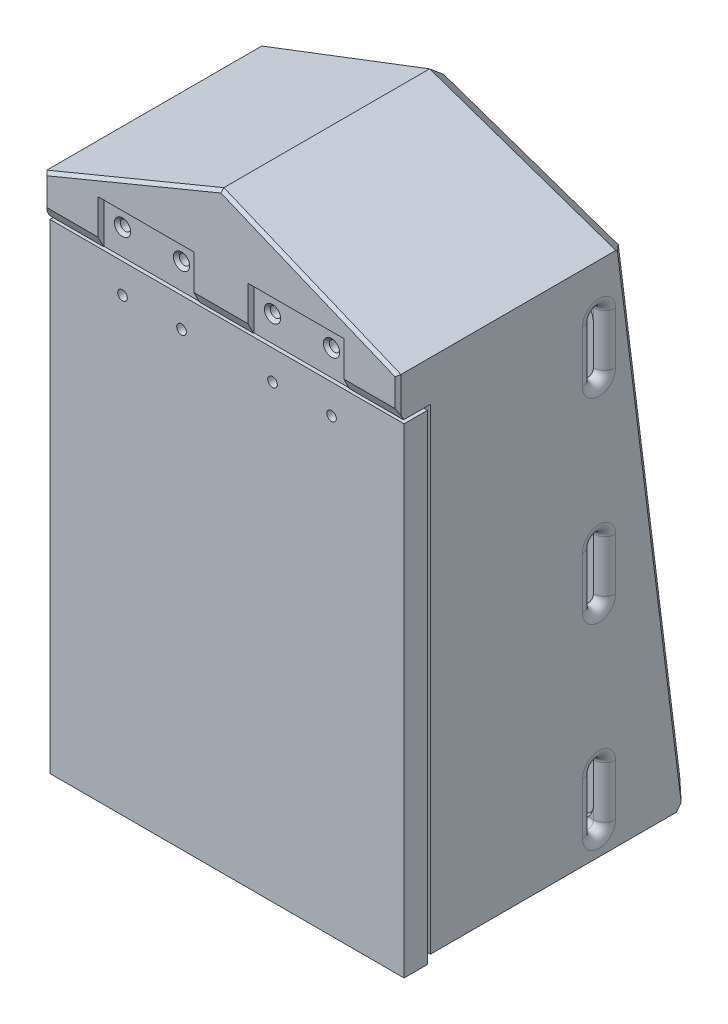
SolidWorks part; units mm, degrees
other "House"
other "Door"
other "Cover" parameters "D1"=134.3446, "D2"=7.568, "D3"=4.0473, "D4"=11.5
ref_plane "Front Plane" through (0, 0, 0) normal (0, 0, 1) x (1, 0, 0)
ref_plane "Top Plane" through (0, 0, 0) normal (0, 1, 0) x (1, 0, 0)
ref_plane "Right Plane" through (0, 0, 0) normal (1, 0, 0) x (0, 0, -1)
sketch "Sketch1" plane through (0, 0, 0) normal (0, 0, 1) x (1, 0, 0)
  line L0 (-48, 73.5589) -> (-48, -66.5589)
  line L1 (-45, -61.5589) -> (45, -61.5589)
  line L2 (-45, -61.5589) -> (-45, 61.5589)
  line L3 (-45, 61.5589) -> (45, 61.5589)
  line L4 (45, -61.5589) -> (45, 61.5589)
  line L5 (0, 61.5589) -> (0, -61.5589) construction
  line L6 (-45, 0) -> (45, 0) construction
  line L7 (-48, -66.5589) -> (48, -66.5589)
  line L8 (48, -66.5589) -> (48, 73.5589)
  line L9 (48, 73.5589) -> (0, 93.4411)
  line L10 (0, 93.4411) -> (-48, 73.5589)
  point P0 (0, 0)
  dimension "D1" = 160
  dimension "D2" = 90
  dimension "D3" = 22.5
  dimension "D4" = 12
  dimension "D5" = 5
  dimension "D6" = 3
  dimension "D7" = 123.1177
extrude "main-extrude" add sketch "Sketch1" along normal blind 60
sketch "Sketch2" plane through (0, 0, 0) normal (0, 0, 1) x (1, 0, 0)
  line L0 (48, -66.5589) -> (48, 73.5589) construction
  line L1 (-48, -66.5589) -> (48, -66.5589) construction
  line L2 (-48, 73.5589) -> (-48, -66.5589) construction
  line L3 (48, 73.5589) -> (0, 93.4411) construction
  line L4 (0, 93.4411) -> (-48, 73.5589) construction
  line L5 (48, -66.5589) -> (48, 73.5589)
  line L6 (-48, -66.5589) -> (48, -66.5589)
  line L7 (-48, 73.5589) -> (-48, -66.5589)
  line L8 (48, 73.5589) -> (0, 93.4411)
  line L9 (0, 93.4411) -> (-48, 73.5589)
extrude "rear-extrude" add sketch "Sketch2" against normal blind 20
sketch "Sketch24" plane through (0, 0, 0) normal (1, 0, 0) x (0, 0, -1)
  line L0 (0, 93.4411) -> (20, -66.5589)
  line L1 (-60, 93.4411) -> (20, 93.4411) construction
  line L2 (20, -66.5589) -> (20, 93.4411)
  line L3 (20, 93.4411) -> (0, 93.4411)
  point P4 (0, 0)
  point P7 (0, 0)
extrude "rear-angle-cut" cut sketch "Sketch24" against normal through all both and the other way through all
sketch "Sketch6" [suppressed] plane through (0, -66.5589, 0) normal (0, -1, 0) x (1, 0, 0)
  line L0 (48, 22.9375) -> (52, 22.9375)
  line L1 (62.9375, 15) -> (62.9375, 22.9375)
  line L2 (52, 22.9375) -> (55, 22.9375)
  line L3 (-48, -5) -> (48, -5) construction
  line L4 (62.9375, 15) -> (62.9375, -5)
  line L5 (62.9375, -5) -> (48, -5)
  line L6 (48, 60) -> (48, -5) construction
  line L7 (48, -5) -> (48, 22.9375)
  line L8 (62.9375, 22.9375) -> (55, 22.9375)
  circle A0 centre (62.9375, 22.9375) radius 7.9375 construction
  arc A1 (62.9375, 15) -> (55, 22.9375) centre (62.9375, 22.9375) cw construction
  point P3 (62.9375, 15)
  dimension "D3" = 15.875
  dimension "D1" = 4
  dimension "D2" = 3
  dimension "D4" = 20
extrude "Boss-Extrude3" [suppressed] add sketch "Sketch6" against normal up to surface (140.1177 mm away)
sketch "Sketch19" [suppressed] plane through (62.9375, 0, 0) normal (1, 0, 0) x (0, 0, -1)
  line L0 (-7.4977, -71.6348) -> (-21.3388, 52.9783) construction
  line L2 (-22.9375, 67.3716) -> (-32.8764, 66.2676) construction
  line L3 (-7.9389, -67.6628) -> (2, -66.5589) construction
  line L6 (5, -66.5589) -> (-22.9375, -66.5589) construction
  dimension "D1" = 10
  dimension "D3" = 3
ref_plane "Plane6" [suppressed] through (62.9375, -67.6628, 7.9389) normal (0, 0.9939, 0.1104) x (1, 0, 0)
sketch "Sketch20" [suppressed] plane through (62.9375, -67.6628, 7.9389) normal (0, 0.9939, 0.1104) x (1, 0, 0)
  line L0 (10, 0) -> (10, -24.5702)
  line L3 (10, -24.5702) -> (-14.9375, -24.5702)
  line L4 (21.2132, 0) -> (-21.2132, 42.4264)
  line L5 (-21.2132, 42.4264) -> (21.2132, 42.4264)
  line L6 (21.2132, 42.4264) -> (21.2132, 0)
  line L7 (0, 0) -> (10.6066, 10.6066) construction
  line L8 (-10, 0) -> (-10, -5)
  line L9 (-10, -5) -> (-14.9375, -5)
  line L10 (-14.9375, -5) -> (-14.9375, -24.5702)
  circle A0 centre (0, 0) radius 10 construction
  circle A3 centre (0, 0) radius 15 construction
  arc A4 (-10, 0) -> (10, 0) centre (0, 0) cw
  point P16 (10.6066, 10.6066)
  point P18 (10.6066, 10.6066)
  point P19 (10.6066, 10.6066)
  point P20 (10.6066, 10.6066)
  point P21 (10.6066, 10.6066)
  point P22 (7.0711, 7.0711)
  dimension "D1" = 20
  dimension "D2" = 5
  dimension "D3" = 5
extrude "Cut-Extrude9" [suppressed] cut sketch "Sketch20" along normal through all
ref_plane "Plane1" [suppressed] through (62.9375, -47.7851, 10.1468) normal (0, 0.9939, 0.1104) x (1, 0, 0)
ref_plane "Plane2" [suppressed] through (0, 0, 0) normal (0, 0.9939, 0.1104) x (1, 0, 0)
sketch "Sketch7" [suppressed] plane through (62.9375, -47.7851, 10.1468) normal (0, 0.9939, 0.1104) x (1, 0, 0)
  line L0 (-14.9375, -15) -> (-11.9375, -15)
  line L2 (-14.9375, -5) -> (-10, -5) construction
  line L4 (-11.9375, -15) -> (-11.9375, -5)
  line L5 (-11.9375, -5) -> (-11.9375, 0)
  line L6 (-14.9375, -15) -> (-14.9375, 0)
  line L7 (0, 11.9375) -> (10, 11.9375)
  line L8 (10, 11.9375) -> (10, 14.9375)
  line L9 (10, 14.9375) -> (0, 14.9375)
  line L10 (-14.9375, -51.6211) -> (-14.9375, -5) construction
  arc A2 (-11.9375, 0) -> (0, 11.9375) centre (0, 0) cw
  arc A3 (0, 14.9375) -> (-14.9375, 0) centre (0, 0) ccw
  circle A4 centre (0, 0) radius 10 construction
  dimension "D1" = 3
  dimension "D2" = 10
  dimension "D3" = 10
extrude "Cut-Extrude10" [suppressed] cut sketch "Sketch7" along normal blind 14
pattern_linear "LPattern1" [suppressed] count 2 spacing 95 along (0, 0.9939, 0.1104)
fillet "Fillet2" [suppressed] radius 3
sketch "Sketch9" plane through (0, -66.5589, 0) normal (0, -1, 0) x (1, 0, 0)
  line L0 (-48, 0) -> (48, 0) construction
  line L3 (-30, 3) -> (0, 3) construction
  line L4 (0, 3) -> (30, 3) construction
  circle A0 centre (-30, 3) radius 3
  circle A1 centre (0, 3) radius 3
  circle A2 centre (30, 3) radius 3
  dimension "D1" = 6
  dimension "D2" = 30
extrude "inner-drain-holes" cut sketch "Sketch9" against normal blind 15
sketch "Sketch4" plane through (0, 0, 60) normal (0, 0, 1) x (1, 0, 0)
  line L0 (-48, 73.5589) -> (-48, -66.5589) construction
  line L1 (-48, 61.5589) -> (48, 61.5589) construction
  line L2 (-48, 61.5589) -> (-48, -66.5589)
  line L3 (-48, -66.5589) -> (48, -66.5589)
  line L4 (48, 61.5589) -> (48, -66.5589)
  line L5 (48, -66.5589) -> (48, 73.5589) construction
  line L6 (-48, 61.5589) -> (-48, 62.5589)
  line L7 (-48, 73.5589) -> (-48, -66.5589) construction
  line L8 (-48, 62.5589) -> (48, 62.5589)
  line L9 (48, -66.5589) -> (48, 73.5589) construction
  line L10 (48, 62.5589) -> (48, 61.5589)
  dimension "D1" = 1
extrude "Cut-Extrude2" cut sketch "Sketch4" against normal blind 8
sketch "Sketch5" plane through (0, 0, 60) normal (0, 0, 1) x (1, 0, 0)
  line L0 (-33.3333, 61.5589) -> (-7.3333, 61.5589) construction
  line L1 (-33.3333, 48.0589) -> (-7.3333, 48.0589)
  line L2 (-33.3333, 48.0589) -> (-33.3333, 75.0589)
  line L3 (-33.3333, 75.0589) -> (-7.3333, 75.0589)
  line L4 (-7.3333, 48.0589) -> (-7.3333, 75.0589)
  line L5 (-20.3333, 75.0589) -> (-20.3333, 48.0589) construction
  line L6 (-33.3333, 61.5589) -> (-7.3333, 61.5589) construction
  line L7 (-45, 61.5589) -> (45, 61.5589) construction
  line L8 (-48, 61.5589) -> (48, 61.5589) construction
  line L9 (0, -987.8214) -> (0, 49012.1786) construction
  line L10 (-33.3333, 61.5589) -> (-48, 61.5589) construction
  line L11 (-48, 73.5589) -> (-48, -66.5589) construction
  line L12 (33.3333, 75.0589) -> (7.3333, 75.0589)
  line L13 (7.3333, 48.0589) -> (7.3333, 75.0589)
  line L14 (33.3333, 48.0589) -> (7.3333, 48.0589)
  line L15 (33.3333, 48.0589) -> (33.3333, 75.0589)
  line L16 (-7.3333, 61.5589) -> (7.3333, 61.5589) construction
  point P0 (-20.3333, 61.5589)
  dimension "D1" = 27
  dimension "D2" = 26
extrude "Cut-Extrude3" cut sketch "Sketch5" against normal offset from surface (1.65 mm away) 6.35 up to face at (0, 0, 52)
sketch "Sketch15" plane through (0, 0, 58.35) normal (0, 0, 1) x (1, 0, 0)
  line L0 (-28.3333, 69.5589) -> (-12.3333, 69.5589) construction
  line L1 (0, -934.1648) -> (0, 49065.8352) construction
  line L2 (0, -200987.8214) -> (0, 249012.1786) construction
  line L3 (-20.3333, 75.0589) -> (-20.3333, 48.0589) construction
  line L4 (-33.3333, 61.5589) -> (-7.3333, 61.5589) construction
  circle A0 centre (-28.3333, 69.5589) radius 1.4
  circle A1 centre (-12.3333, 69.5589) radius 1.4
  circle A2 centre (28.3333, 69.5589) radius 1.4
  circle A3 centre (12.3333, 69.5589) radius 1.4
  point P8 (-20.3333, 69.5589)
  dimension "D1" = 2.8
  dimension "D2" = 16
  dimension "D3" = 8
extrude "Cut-Extrude7" cut sketch "Sketch15" against normal blind 40
sketch "Sketch12" plane through (0, 0, 52) normal (0, 0, 1) x (1, 0, 0)
  line L5 (0, 61.5589) -> (0, -61.5589) construction
  line L6 (-48.001, 61.5589) -> (48.001, 61.5589)
  line L7 (-48.001, 61.5589) -> (-48.001, -68.5589)
  line L8 (-48.001, -68.5589) -> (48.001, -68.5589)
  line L9 (48.001, 61.5589) -> (48.001, -68.5589)
  line L10 (0, -68.5589) -> (0, 61.5589) construction
  line L11 (-48.001, -3.5) -> (48.001, -3.5) construction
  line L12 (-48, -66.5589) -> (48, -66.5589) construction
  line L13 (-48, 73.5589) -> (-48, -66.5589) construction
  point P0 (0, -3.5)
  dimension "D1" = 2
  dimension "D2" = 0.001
extrude "Boss-Extrude5" add sketch "Sketch12" along normal blind 6.35 separate body
sketch "Sketch13" plane through (0, 0, 58.35) normal (0, 0, 1) x (1, 0, 0)
  line L0 (-1053.3426, 61.5589) -> (48946.6574, 61.5589) construction
  line L1 (-33.3333, 61.5589) -> (-48, 61.5589) construction
  line L4 (7.3333, 48.0589) -> (33.3333, 48.0589)
  line L5 (33.3333, 48.0589) -> (33.3333, 75.0589)
  line L6 (33.3333, 75.0589) -> (7.3333, 75.0589)
  line L7 (7.3333, 75.0589) -> (7.3333, 48.0589)
  line L8 (7.3333, 48.0589) -> (33.3333, 48.0589) construction
  line L9 (33.3333, 48.0589) -> (33.3333, 75.0589) construction
  line L10 (33.3333, 75.0589) -> (7.3333, 75.0589) construction
  line L11 (7.3333, 75.0589) -> (7.3333, 48.0589) construction
  line L12 (-33.3333, 48.0589) -> (-7.3333, 48.0589)
  line L13 (-33.3333, 75.0589) -> (-33.3333, 48.0589)
  line L14 (-7.3333, 75.0589) -> (-33.3333, 75.0589)
  line L15 (-7.3333, 48.0589) -> (-7.3333, 75.0589)
  line L16 (-33.3333, 48.0589) -> (-7.3333, 48.0589) construction
  line L17 (-33.3333, 75.0589) -> (-33.3333, 48.0589) construction
  line L18 (-7.3333, 75.0589) -> (-33.3333, 75.0589) construction
  line L19 (-7.3333, 48.0589) -> (-7.3333, 75.0589) construction
  circle A0 centre (28.3333, 69.5589) radius 1.4 construction
  circle A1 centre (12.3333, 69.5589) radius 1.4 construction
  circle A2 centre (-28.3333, 69.5589) radius 1.4 construction
  circle A3 centre (-12.3333, 69.5589) radius 1.4 construction
  circle A4 centre (28.3333, 69.5589) radius 1.4 construction
  circle A5 centre (12.3333, 69.5589) radius 1.4 construction
  circle A6 centre (-28.3333, 69.5589) radius 1.4 construction
  circle A7 centre (-12.3333, 69.5589) radius 1.4 construction
  circle A8 centre (28.3333, 53.5589) radius 1.4 construction
  circle A9 centre (12.3333, 53.5589) radius 1.4 construction
  circle A10 centre (-12.3333, 53.5589) radius 1.4 construction
  circle A11 centre (-28.3333, 53.5589) radius 1.4 construction
  circle A12 centre (-28.3333, 53.5589) radius 1.3
  circle A13 centre (-12.3333, 53.5589) radius 1.3
  circle A14 centre (12.3333, 53.5589) radius 1.3
  circle A15 centre (28.3333, 53.5589) radius 1.3
  dimension "D3" = 2.6
  dimension "D1" = 0
  dimension "D2" = 0
extrude "Cut-Extrude8" cut sketch "Sketch13" against normal through all
chamfer "Chamfer4" distance 3 distance2 1.5 3 edges at (0, 62.5589, 60) (-40.6667, 62.5589, 60) (40.6667, 62.5589, 60)
chamfer "Chamfer7" distance 0.8 angle 45 4 edges at (26.9333, 69.5589, 58.35) (10.9333, 69.5589, 58.35) (-10.9333, 69.5589, 58.35) (-26.9333, 69.5589, 58.35)
fillet "cavity-fillet" radius 5 4 edges at (45, -61.5589, 26) (-45, -61.5589, 26) (45, 61.5589, 26) (-45, 61.5589, 26)
sketch "Sketch21" plane through (0, 0, 0) normal (0, 0, 1) x (1, 0, 0)
  line L14 (30, -61.0589) -> (40, -61.0589)
  line L15 (44.5, -56.5589) -> (44.5, 56.5589)
  line L16 (40, 61.0589) -> (-40, 61.0589)
  line L17 (-44.5, 56.5589) -> (-44.5, -56.5589)
  line L18 (-40, -61.0589) -> (-30, -61.0589)
  line L19 (-30, -61.0589) -> (0, -61.0589)
  line L20 (0, -61.0589) -> (30, -61.0589)
  line L21 (30, -61.0589) -> (40, -61.0589)
  line L22 (44.5, -56.5589) -> (44.5, 56.5589)
  line L23 (40, 61.0589) -> (-40, 61.0589)
  line L24 (-44.5, 56.5589) -> (-44.5, -56.5589)
  line L25 (-40, -61.0589) -> (-30, -61.0589)
  line L26 (-30, -61.0589) -> (0, -61.0589)
  line L27 (0, -61.0589) -> (30, -61.0589)
  circle A4 centre (-38.5, 55.0589) radius 6 construction
  circle A5 centre (38.5, 55.0589) radius 6 construction
  circle A6 centre (38.5, -55.0589) radius 6 construction
  circle A7 centre (-38.5, -55.0589) radius 6 construction
  arc A8 (40, -61.0589) -> (44.5, -56.5589) centre (40, -56.5589) ccw
  arc A9 (44.5, 56.5589) -> (40, 61.0589) centre (40, 56.5589) ccw
  arc A10 (-40, 61.0589) -> (-44.5, 56.5589) centre (-40, 56.5589) ccw
  arc A11 (-44.5, -56.5589) -> (-40, -61.0589) centre (-40, -56.5589) ccw
  arc A12 (40, -61.0589) -> (44.5, -56.5589) centre (40, -56.5589) ccw
  arc A13 (44.5, 56.5589) -> (40, 61.0589) centre (40, 56.5589) ccw
  arc A14 (-40, 61.0589) -> (-44.5, 56.5589) centre (-40, 56.5589) ccw
  arc A15 (-44.5, -56.5589) -> (-40, -61.0589) centre (-40, -56.5589) ccw
  circle A17 centre (-38.5, 55.0589) radius 1.3
  circle A18 centre (38.5, 55.0589) radius 1.3
  circle A19 centre (-38.5, -55.0589) radius 1.3
  circle A20 centre (38.5, -55.0589) radius 1.3
  dimension "D2" = 12
  dimension "D5" = 2.6
  dimension "D1" = 0.5
  dimension "D3" = 2
  dimension "D4" = 2
extrude "Boss-Extrude10" add sketch "Sketch21" along normal blind 3 separate body
sketch "Sketch22" plane through (0, 0, 0) normal (0, 0, 1) x (1, 0, 0)
  circle A0 centre (-38.5, 55.0589) radius 2
  circle A1 centre (38.5, 55.0589) radius 2
  circle A2 centre (-38.5, -55.0589) radius 2
  circle A3 centre (38.5, -55.0589) radius 2
  circle A4 centre (-38.5, 55.0589) radius 1.3 construction
  circle A5 centre (38.5, 55.0589) radius 1.3 construction
  circle A6 centre (38.5, -55.0589) radius 1.3 construction
  circle A7 centre (-38.5, -55.0589) radius 1.3 construction
  dimension "D1" = 4
extrude "Cut-Extrude11" cut sketch "Sketch22" against normal through all
chamfer "Chamfer6" distance 0.8 angle 45 11 edges at (-45, 0, 52) (-43.5355, 60.0944, 52) (-43.5355, -60.0944, 52) (0, 61.5589, 52) (0, -61.5589, 52) (43.5355, 60.0944, 52) (43.5355, -60.0944, 52) (45, 0, 52) (-48, -2, 52) (48, -2, 52) (0, -66.5589, 52)
chamfer "Chamfer9" distance 0.8 angle 45 4 edges at (-48, 69.5589, 60) (48, 69.5589, 60) (24, 83.5, 60) (-24, 83.5, 60)
sketch "Sketch23" plane through (0, 0, 0) normal (1, 0, 0) x (0, 0, -1)
  line L0 (-5.5, 46.0589) -> (-5.5, 60.0589) construction
  line L1 (-7, 46.0589) -> (-7, 60.0589)
  line L2 (-4, 46.0589) -> (-4, 60.0589)
  line L4 (0, -61.5589) -> (0, 61.5589) construction
  line L5 (-5.5, -60.0589) -> (-5.5, -46.0589) construction
  line L6 (-7, -60.0589) -> (-7, -46.0589)
  line L7 (-4, -60.0589) -> (-4, -46.0589)
  line L8 (-5.5, 7) -> (-5.5, -7) construction
  line L9 (-4, 7) -> (-4, -7)
  line L10 (-7, 7) -> (-7, -7)
  arc A0 (-7, 46.0589) -> (-4, 46.0589) centre (-5.5, 46.0589) ccw
  arc A1 (-4, 60.0589) -> (-7, 60.0589) centre (-5.5, 60.0589) ccw
  arc A2 (-7, -60.0589) -> (-4, -60.0589) centre (-5.5, -60.0589) ccw
  arc A3 (-4, -46.0589) -> (-7, -46.0589) centre (-5.5, -46.0589) ccw
  arc A4 (-4, 7) -> (-7, 7) centre (-5.5, 7) ccw
  arc A5 (-7, -7) -> (-4, -7) centre (-5.5, -7) ccw
  point P2 (-5.5, 53.0589)
  point P7 (-5.5, 61.5589)
  point P8 (-5.5, -53.0589)
  point P18 (-5.5, -61.5589)
  point P19 (-5.5, 0)
  point P28 (0, 0)
  dimension "D1" = 3
  dimension "D2" = 14
  dimension "D3" = 4
extrude "Cut-Extrude12" cut sketch "Sketch23" against normal through all both and the other way through all
fillet "Fillet3" radius 3 24 edges at (48, -44.5589, 5.5) (48, -53.0589, 7) (48, -61.5589, 5.5) (48, 61.5589, 5.5) (48, 53.0589, 7) (48, 44.5589, 5.5) (-48, 44.5589, 5.5) (-48, 53.0589, 7) (-48, 61.5589, 5.5) (-48, -61.5589, 5.5) (-48, -53.0589, 7) (-48, -44.5589, 5.5) (48, -53.0589, 4) (48, 53.0589, 4) (-48, 53.0589, 4) (-48, -53.0589, 4) (-48, -8.5, 5.5) (-48, 0, 7) (-48, 8.5, 5.5) (48, 8.5, 5.5) (48, 0, 7) (48, -8.5, 5.5) (-48, 0, 4) (48, 0, 4)
chamfer "Chamfer10" distance 5 angle 45 1 edges at (0, -66.5589, -20)
chamfer "Chamfer11" distance 3 angle 45 4 edges at (24, 83.5, -1.2426) (-24, 83.5, -1.2426) (-48, 5.9807, -10.9326) (48, 5.9807, -10.9326)
equation "\"D1@Sketch19\"=\"D4@Sketch6\"/2"
